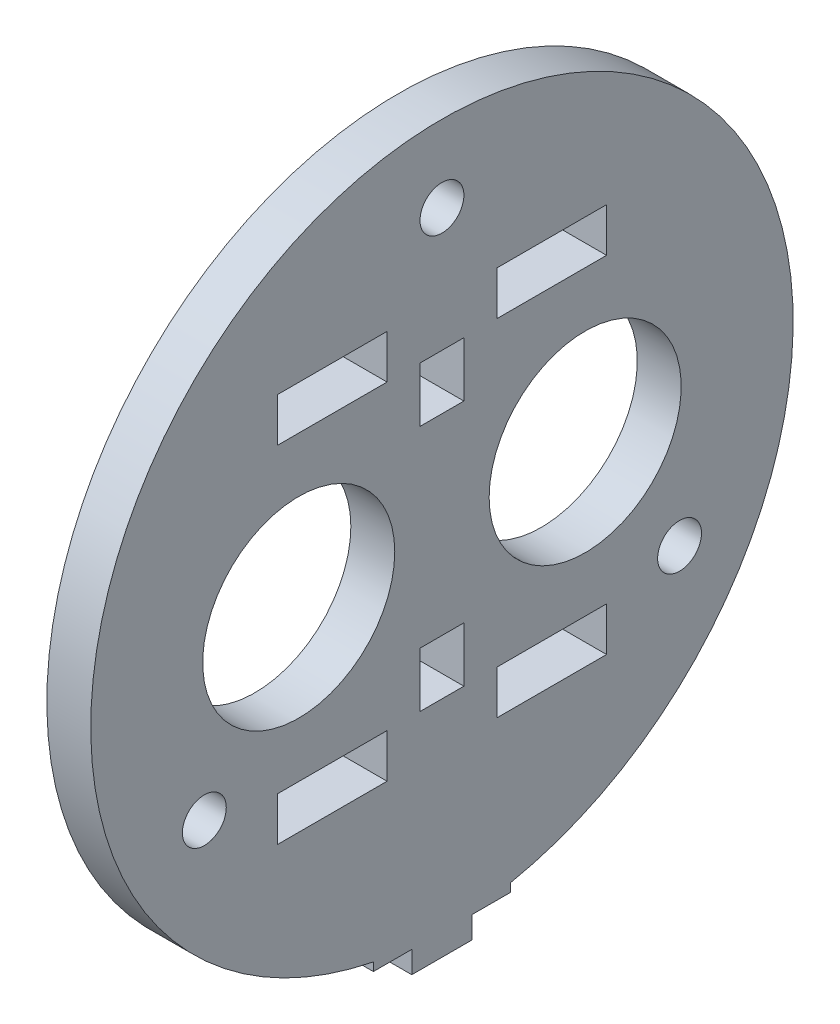
SolidWorks part; units mm, degrees
ref_plane "Front Plane" through (0, 0, 0) normal (0, 0, 1) x (1, 0, 0)
ref_plane "Top Plane" through (0, 0, 0) normal (0, 1, 0) x (1, 0, 0)
ref_plane "Right Plane" through (0, 0, 0) normal (1, 0, 0) x (0, 0, -1)
sketch "Sketch1" plane through (0, 0, 0) normal (1, 0, 0) x (0, 0, -1)
  line L0 (0, 86.3618) -> (0, -95.6447) construction
  line L1 (-89.4162, 0) -> (80.9544, 0) construction
  line L5 (-12.5, -62.7674) -> (-12.5, -68.29)
  line L6 (-12.5, -68.29) -> (12.5, -68.29)
  line L7 (12.5, -62.7674) -> (12.5, -68.29)
  circle A0 centre (0, 0) radius 76.29 construction
  circle A1 centre (0, 50) radius 4
  circle A2 centre (43.3013, -25) radius 4
  circle A3 centre (-43.3013, -25) radius 4
  circle A4 centre (-26.1, 0) radius 17.5
  circle A5 centre (26.1, 0) radius 17.5
  arc A6 (12.5, -62.7674) -> (-12.5, -62.7674) centre (0, 0) ccw
  circle A7 centre (-26.1, 0) radius 22.1 construction
  point P14 (0, 0)
  point P16 (0, -76.29)
  point P20 (-4, 0)
  point P27 (0, -68.29)
  point P30 (0, 56.7762)
  point P31 (0, 56.7762)
  dimension "D1" = 152.58
  dimension "D2" = 8
  dimension "D5" = 35
  dimension "D9" = 8
  dimension "D7" = 64
  dimension "D10" = 44.2
  dimension "D3" = 50
  dimension "D6" = 8
  dimension "D8" = 25
  dimension "D4" = 3
extrude "Boss-Extrude1" add sketch "Sketch1" along normal blind 8
sketch "Sketch2" plane through (0, 0, 0) normal (-1, 0, 0) x (0, 0, 1)
  line L0 (0, -90.2636) -> (0, 91.611) construction
  line L1 (-93.4475, 0) -> (84.8595, 0) construction
  line L2 (10, -27.5) -> (10, -35.5)
  line L3 (-30, -27.5) -> (-10, -27.5)
  line L4 (-30, -27.5) -> (-30, -35.5)
  line L5 (-30, -35.5) -> (-10, -35.5)
  line L6 (-10, -27.5) -> (-10, -35.5)
  line L7 (30, -35.5) -> (10, -35.5)
  line L8 (30, -27.5) -> (30, -35.5)
  line L9 (30, -27.5) -> (10, -27.5)
  line L10 (30, 27.5) -> (10, 27.5)
  line L11 (30, 27.5) -> (30, 35.5)
  line L12 (30, 35.5) -> (10, 35.5)
  line L13 (-10, 27.5) -> (-10, 35.5)
  line L14 (-30, 35.5) -> (-10, 35.5)
  line L15 (-30, 27.5) -> (-30, 35.5)
  line L16 (-30, 27.5) -> (-10, 27.5)
  line L17 (10, 27.5) -> (10, 35.5)
  line L18 (4, 17.5) -> (4, 27.5)
  line L19 (-4, -17.5) -> (4, -17.5)
  line L20 (-4, -17.5) -> (-4, -27.5)
  line L21 (-4, -27.5) -> (4, -27.5)
  line L22 (4, -17.5) -> (4, -27.5)
  line L23 (-4, 27.5) -> (4, 27.5)
  line L24 (-4, 17.5) -> (-4, 27.5)
  line L25 (-4, 17.5) -> (4, 17.5)
  line L26 (5.5, -68.29) -> (5.5, -64.29)
  line L27 (-12.5, -68.29) -> (-5.5, -68.29)
  line L28 (-12.5, -68.29) -> (-12.5, -64.29)
  line L29 (-12.5, -64.29) -> (-5.5, -64.29)
  line L30 (-5.5, -68.29) -> (-5.5, -64.29)
  line L31 (12.5, -64.29) -> (5.5, -64.29)
  line L32 (12.5, -68.29) -> (12.5, -64.29)
  line L33 (12.5, -68.29) -> (5.5, -68.29)
  point P26 (0, -17.5)
  dimension "D1" = 27.5
  dimension "D2" = 20
  dimension "D3" = 20
  dimension "D4" = 8
  dimension "D5" = 8
  dimension "D6" = 10
  dimension "D7" = 4
  dimension "D8" = 7
extrude "Cut-Extrude1" cut sketch "Sketch2" against normal up to next
